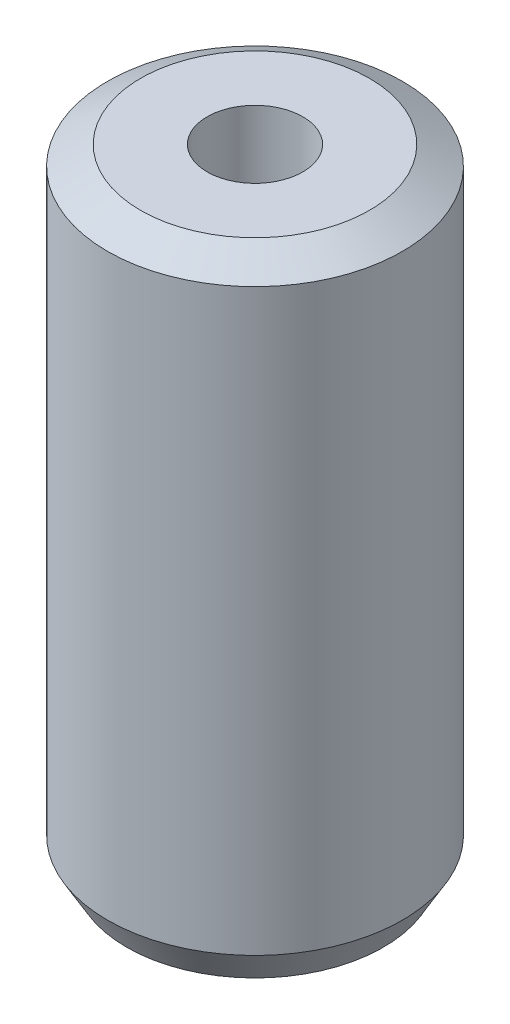
SolidWorks part; units mm, degrees
ref_plane "Front Plane" through (0, 0, 0) normal (0, 0, 1) x (1, 0, 0)
ref_plane "Top Plane" through (0, 0, 0) normal (0, 1, 0) x (1, 0, 0)
ref_plane "Right Plane" through (0, 0, 0) normal (1, 0, 0) x (0, 0, -1)
sketch "Sketch1" plane through (0, 0, 0) normal (0, 1, 0) x (1, 0, 0)
  circle A0 centre (0, 0) radius 42.5
  dimension "SHAFT_OD" = 85
extrude "Boss-Extrude1" add sketch "Sketch1" along normal blind 182.0012
sketch "Sketch2" plane through (0, 0, 0) normal (0, 1, 0) x (1, 0, 0)
  circle A0 centre (0, 0) radius 13.7906
  dimension "BORE_D" = 27.5812
extrude "Cut-Extrude1" cut sketch "Sketch2" along normal through all
chamfer "Chamfer1" distance 5.4902 angle 60 2 edges at (0, 182.0012, 42.5) (0, 0, 42.5) first distance on face at (0, 182.0012, 42.5) first distance on face at (0, 0, 13.7906)
